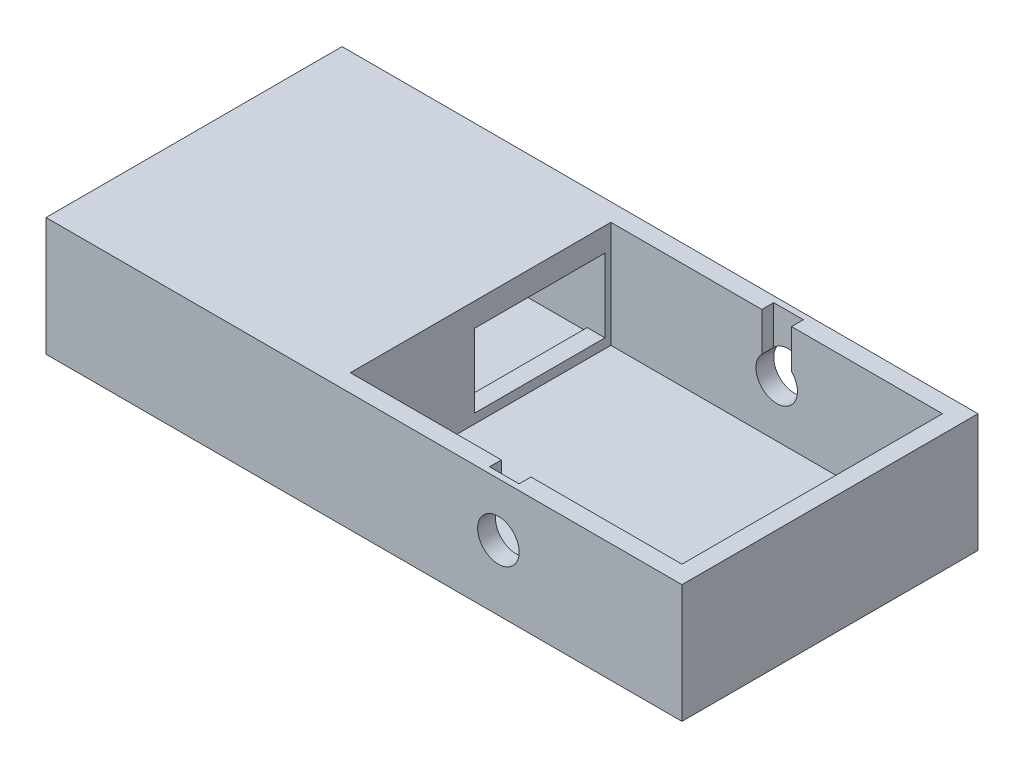
SolidWorks part; units mm, degrees
ref_plane "Front" through (0, 0, 0) normal (0, 0, 1) x (1, 0, 0)
ref_plane "Top" through (0, 0, 0) normal (0, 1, 0) x (1, 0, 0)
ref_plane "Right" through (0, 0, 0) normal (1, 0, 0) x (0, 0, -1)
sketch "Sketch1" plane through (0, 0, 0) normal (0, 1, 0) x (1, 0, 0)
  line L1 (-39.37, 31.75) -> (39.37, 31.75)
  line L2 (-39.37, 31.75) -> (-39.37, -31.75)
  line L3 (-39.37, -31.75) -> (39.37, -31.75)
  line L4 (39.37, 31.75) -> (39.37, -31.75)
  line L5 (-39.37, 31.75) -> (39.37, -31.75) construction
  line L6 (-39.37, -31.75) -> (39.37, 31.75) construction
  line L7 (-35.56, 27.94) -> (35.56, 27.94)
  line L8 (-35.56, 27.94) -> (-35.56, -27.94)
  line L9 (-35.56, -27.94) -> (35.56, -27.94)
  line L10 (35.56, 27.94) -> (35.56, -27.94)
  line L11 (-35.56, 27.94) -> (35.56, -27.94) construction
  line L12 (-35.56, -27.94) -> (35.56, 27.94) construction
  point P0 (0, 0)
  point P6 (0, 0)
  dimension "D1" = 63.5
  dimension "D2" = 78.74
  dimension "D3" = 55.88
  dimension "D4" = 71.12
extrude "pcb-base" add sketch "Sketch1" along normal blind 2.54 contours L8 L7 L10 L9
extrude "pcb-wall" add sketch "Sketch1<4>" along normal blind 25.4
sketch "Sketch1<4>" plane through (0, 0, 0) normal (0, 1, 0) x (1, 0, 0) same geometry as "Sketch1"
sketch "Sketch2" plane through (-39.37, 0, 0) normal (-1, 0, 0) x (0, 0, 1)
  line L0 (-31.75, 25.4) -> (31.75, 25.4) construction
  line L1 (-26.67, 4.572) -> (1.27, 4.572)
  line L2 (-26.67, 4.572) -> (-26.67, 20.32)
  line L3 (-26.67, 20.32) -> (1.27, 20.32)
  line L4 (1.27, 4.572) -> (1.27, 20.32)
  line L5 (-26.67, 4.572) -> (1.27, 20.32) construction
  line L6 (-26.67, 20.32) -> (1.27, 4.572) construction
  line L7 (31.75, 25.4) -> (31.75, 0) construction
  line L8 (-31.75, 25.4) -> (-31.75, 0) construction
  line L9 (-31.75, 0) -> (31.75, 0) construction
  point P0 (-12.7, 12.446)
  dimension "D1" = 5.08
  dimension "0.35" = 30.48
  dimension "D3" = 5.08
  dimension "0.175" = 4.572
extrude "pcb-gap" cut sketch "Sketch2" against normal up to vertex (3.81 mm away) up to point (-35.56, 25.4, 27.94)
sketch "Sketch3" plane through (0, 0, -27.94) normal (0, 0, 1) x (1, 0, 0)
  line L0 (-35.56, 25.4) -> (-35.56, 2.54) construction
  line L2 (-3.175, 13.97) -> (3.175, 13.97)
  line L3 (35.56, 25.4) -> (-35.56, 25.4) construction
  line L4 (-3.175, 13.97) -> (-3.175, 25.4)
  line L5 (-3.175, 25.4) -> (3.175, 25.4)
  line L6 (3.175, 13.97) -> (3.175, 25.4)
  line L7 (-3.175, 13.97) -> (3.175, 25.4) construction
  line L8 (-3.175, 25.4) -> (3.175, 13.97) construction
  circle A0 centre (0, 13.97) radius 4.445
  point P7 (0, 19.685)
  line M4 (35.56, 25.4) -> (-35.56, 25.4)
  dimension "D2" = 8.89
  dimension "D1" = 35.56
  dimension "D3" = 11.43
  dimension "D4" = 6.35
sketch "Sketch4" plane through (0, 0, 27.94) normal (0, 0, -1) x (-1, 0, 0)
  line L0 (35.56, 25.4) -> (-35.56, 25.4) construction
  line L1 (-3.175, 25.4) -> (3.175, 25.4)
  line L2 (-3.175, 25.4) -> (-3.175, 13.97)
  line L3 (-3.175, 13.97) -> (3.175, 13.97)
  line L4 (3.175, 25.4) -> (3.175, 13.97)
  line L5 (-3.175, 25.4) -> (3.175, 13.97) construction
  line L6 (-3.175, 13.97) -> (3.175, 25.4) construction
  circle A0 centre (0, 13.97) radius 4.445
  point P2 (0, 19.685)
  line M4 (35.56, 25.4) -> (-35.56, 25.4)
  dimension "D1" = 8.89
  dimension "D2" = 6.35
  dimension "D3" = 3.175
extrude "lid-hole-1" cut sketch "Sketch4" against normal blind 3.81 contours L2 A0 L4 L3 | L4 A0 L2 L3 region at (0, 16.004, 27.94) region at (0, 12.5426, 27.94)
extrude "hole-slide-1" cut sketch "Sketch4<6>" against normal blind 2.54 contours A0 L4 L2 M4 region at (0, 21.6904, 27.94)
sketch "Sketch4<6>" plane through (0, 0, 27.94) normal (0, 0, -1) x (-1, 0, 0) same geometry as "Sketch4"
extrude "lid-hole-2" cut sketch "Sketch3" against normal blind 3.81 contours L4 A0 L6 L2 | L6 A0 L4 L2 region at (0, 16.004, -27.94) region at (0, 12.5426, -27.94)
extrude "hole-slide-2" cut sketch "Sketch3<5>" against normal blind 2.54 contours A0 L6 L4 M4 region at (0, 21.6904, -27.94)
sketch "Sketch3<5>" plane through (0, 0, -27.94) normal (0, 0, 1) x (1, 0, 0) same geometry as "Sketch3"
sketch "Sketch5" plane through (-39.37, 0, 0) normal (-1, 0, 0) x (0, 0, 1)
  line L0 (31.75, 25.4) -> (31.75, 0) construction
  line L1 (-31.75, 0) -> (31.75, 0)
  line L2 (-31.75, 0) -> (-31.75, 3.81)
  line L3 (-31.75, 3.81) -> (31.75, 3.81)
  line L4 (31.75, 0) -> (31.75, 3.81)
  line L5 (1.27, 20.32) -> (-26.67, 20.32) construction
  line L6 (-31.75, 25.4) -> (31.75, 25.4) construction
  line L7 (-31.75, 0) -> (6.35, 0)
  line L8 (-31.75, 0) -> (-31.75, 3.81)
  line L9 (-31.75, 3.81) -> (6.35, 3.81)
  line L10 (6.35, 0) -> (6.35, 3.81)
  line L11 (-31.75, 3.81) -> (-26.67, 3.81)
  line L12 (-31.75, 3.81) -> (-31.75, 25.4)
  line L13 (-31.75, 25.4) -> (-26.67, 25.4)
  line L14 (-26.67, 3.81) -> (-26.67, 25.4)
  line L15 (6.35, 3.81) -> (1.27, 3.81)
  line L16 (6.35, 3.81) -> (6.35, 25.4)
  line L17 (6.35, 25.4) -> (1.27, 25.4)
  line L18 (1.27, 3.81) -> (1.27, 25.4)
  line L19 (-26.67, 25.4) -> (1.27, 25.4)
  line L20 (-26.67, 25.4) -> (-26.67, 20.32)
  line L21 (-26.67, 20.32) -> (1.27, 20.32)
  line L22 (1.27, 25.4) -> (1.27, 20.32)
  line M13 (-26.67, 20.32) -> (1.27, 20.32)
  line M14 (1.27, 20.32) -> (1.27, 4.572)
  line M16 (-26.67, 4.572) -> (-26.67, 20.32)
  line M17 (-31.75, 0) -> (31.75, 0)
  line M19 (31.75, 25.4) -> (-31.75, 25.4)
  line M20 (-31.75, 25.4) -> (-31.75, 0)
  dimension "D1" = 3.81
  dimension "D2" = 38.1
  dimension "D3" = 5.08
  dimension "D4" = 5.08
extrude "battery-compartment" add sketch "Sketch5" along normal blind 48.768 contours L3 L14 M16 M19 M20 | L18 L14 M13 M19 | L18 L3 L16 M19 M14 | L10 L3 L9 M17 M20 region at (-39.37, 1.905, -12.7) region at (-39.37, 14.605, -29.21) region at (-39.37, 14.605, 3.81) region at (-39.37, 22.86, -12.7)
sketch "Sketch7" plane through (-88.138, 0, 0) normal (-1, 0, 0) x (0, 0, 1)
  line L1 (-31.75, 25.4) -> (6.35, 25.4)
  line L2 (-31.75, 25.4) -> (-31.75, 0)
  line L3 (-31.75, 0) -> (6.35, 0)
  line L4 (6.35, 25.4) -> (6.35, 0)
extrude "battery-compartment-wall" add sketch "Sketch7" along normal blind 8.89 and the other way blind 1.27
sketch "Sketch8" plane through (0, 0, 6.35) normal (0, 0, 1) x (1, 0, 0)
  line L0 (-97.028, 0) -> (-39.37, 0) construction
  line L1 (-97.028, 25.4) -> (-94.488, 25.4)
  line L2 (-97.028, 25.4) -> (-97.028, 0)
  line L3 (-97.028, 0) -> (-94.488, 0)
  line L4 (-94.488, 25.4) -> (-94.488, 0)
  line L5 (-39.37, 0) -> (-39.37, 25.4) construction
  line L6 (-97.028, 25.4) -> (-39.37, 25.4)
  line L7 (-97.028, 25.4) -> (-97.028, 22.86)
  line L8 (-97.028, 22.86) -> (-39.37, 22.86)
  line L9 (-39.37, 25.4) -> (-39.37, 22.86)
  line L15 (-97.028, 0) -> (-39.37, 0)
  line L16 (-97.028, 0) -> (-97.028, 2.54)
  line L17 (-97.028, 2.54) -> (-39.37, 2.54)
  line L18 (-39.37, 0) -> (-39.37, 2.54)
  line M10 (-97.028, 0) -> (-39.37, 0)
  line M11 (-39.37, 0) -> (-39.37, 25.4)
  dimension "D1" = 2.54
  dimension "D3" = 2.54
  dimension "D4" = 2.54
extrude "empty-compartment" add sketch "Sketch8" along normal blind 25.4 contours L2 L17 L4 L8 | L17 L4 M10 M11 | L2 L1 L4 L3 | L7 L8 L9 L6 region at (-95.758, 12.7, 6.35) region at (-66.929, 1.27, 6.35)
sketch "Sketch9" plane through (0, 0, 31.75) normal (0, 0, 1) x (1, 0, 0)
  line L0 (-97.028, 0) -> (39.37, 0) construction
  line L1 (-97.028, 25.4) -> (-39.37, 25.4)
  line L2 (-97.028, 25.4) -> (-97.028, 0)
  line L3 (-97.028, 0) -> (-39.37, 0)
  line L4 (-39.37, 25.4) -> (-39.37, 0)
extrude "empty-compartment-wall" add sketch "Sketch9" against normal blind 3.81
